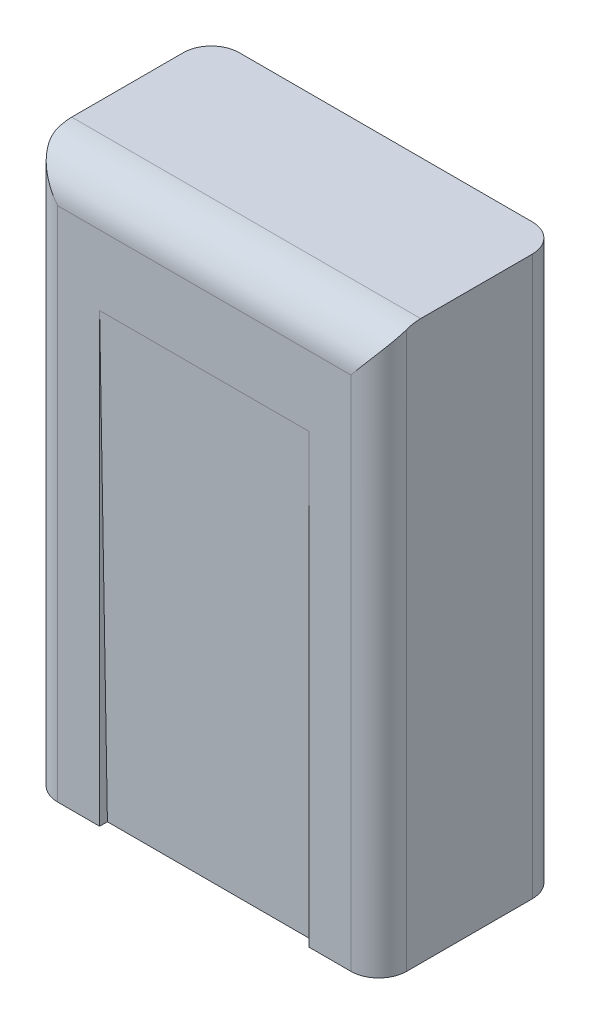
SolidWorks part; units mm, degrees
material "K110"
ref_plane "Front Plane" through (0, 0, 0) normal (0, 0, 1) x (1, 0, 0)
ref_plane "Top Plane" through (0, 0, 0) normal (0, 1, 0) x (1, 0, 0)
ref_plane "Right Plane" through (0, 0, 0) normal (1, 0, 0) x (0, 0, -1)
sketch "Sketch1" plane through (0, 0, 0) normal (0, 1, 0) x (1, 0, 0)
  line L1 (-12.5, -6.5) -> (12.5, -6.5)
  line L2 (-12.5, -6.5) -> (-12.5, 6.5)
  line L3 (-12.5, 6.5) -> (12.5, 6.5)
  line L4 (12.5, -6.5) -> (12.5, 6.5)
  line L5 (-12.5, -6.5) -> (12.5, 6.5) construction
  line L6 (-12.5, 6.5) -> (12.5, -6.5) construction
  point P0 (0, 0)
  dimension "D1" = 13
  dimension "D2" = 25
extrude "Boss-Extrude1" add sketch "Sketch1" against normal blind 40
fillet "Fillet1" radius 2 4 edges at (-12.5, -20, -6.5) (-12.5, -20, 6.5) (12.5, -20, -6.5) (12.5, -20, 6.5)
fillet "Fillet2" radius 3 1 edges at (0, 0, 6.5) tangent propagation no
hole_wizard "M6 Tapped Hole1" positions "Sketch4" profile "Sketch3" tap size "M6" standard "ISO"
sketch "Sketch4" plane through (0, -40, 0) normal (0, -1, 0) x (-1, 0, 0)
  line L0 (-12.5, -4.5) -> (-12.5, 4.5) construction
  line L1 (12.5, 4.5) -> (12.5, -4.5) construction
  point P0 (-5, 0)
  point P2 (5, 0)
  dimension "D1" = 7.5
  dimension "D2" = 7.5
sketch "Sketch3" plane through (5, -40, 0) normal (1, 0, 0) x (0, 0, -1)
  line L0 (0, 0) -> (0, 18.5022)
  line L1 (0, 18.5022) -> (2.5, 17)
  line L2 (2.5, 17) -> (2.5, 0.525)
  line L3 (2.5, 0.525) -> (3.025, 0)
  line L5 (3.025, 0) -> (0, 0)
  line L6 (-2.5, 0.525) -> (-3.025, 0) construction
  line L10 (0, 18.5022) -> (-2.5, 17) construction
  line L11 (0, -6.35) -> (0, 107.95) construction
  dimension "Tap Drill Dia." = 5
  dimension "Tap Drill Depth" = 17
  dimension "Near C'Sink Dia." = 6.05
  dimension "Near C'Sink Angle" = 90
  dimension "Drill Angle" = 118
cosmetic thread "Hole Thread1" parameters "D1"=12, "D2"=6
cosmetic thread "Hole Thread2" parameters "D1"=12, "D2"=6
sketch "Sketch5" plane through (0, 0, 0) normal (1, 0, 0) x (0, 0, -1)
  line L4 (-6.5, -8) -> (-5.9414, -40)
  line L5 (-6.5, -40) -> (-6.5, -3) construction
  line L6 (-6.5, -40) -> (-4.5, -40) construction
  line L7 (-5.9414, -40) -> (-6.5, -40)
  line L8 (-6.5, -40) -> (-6.5, -8)
  dimension "D1" = 5
  dimension "D2" = 1
extrude "Cut-Extrude1" cut sketch "Sketch5" against normal mid plane 15
